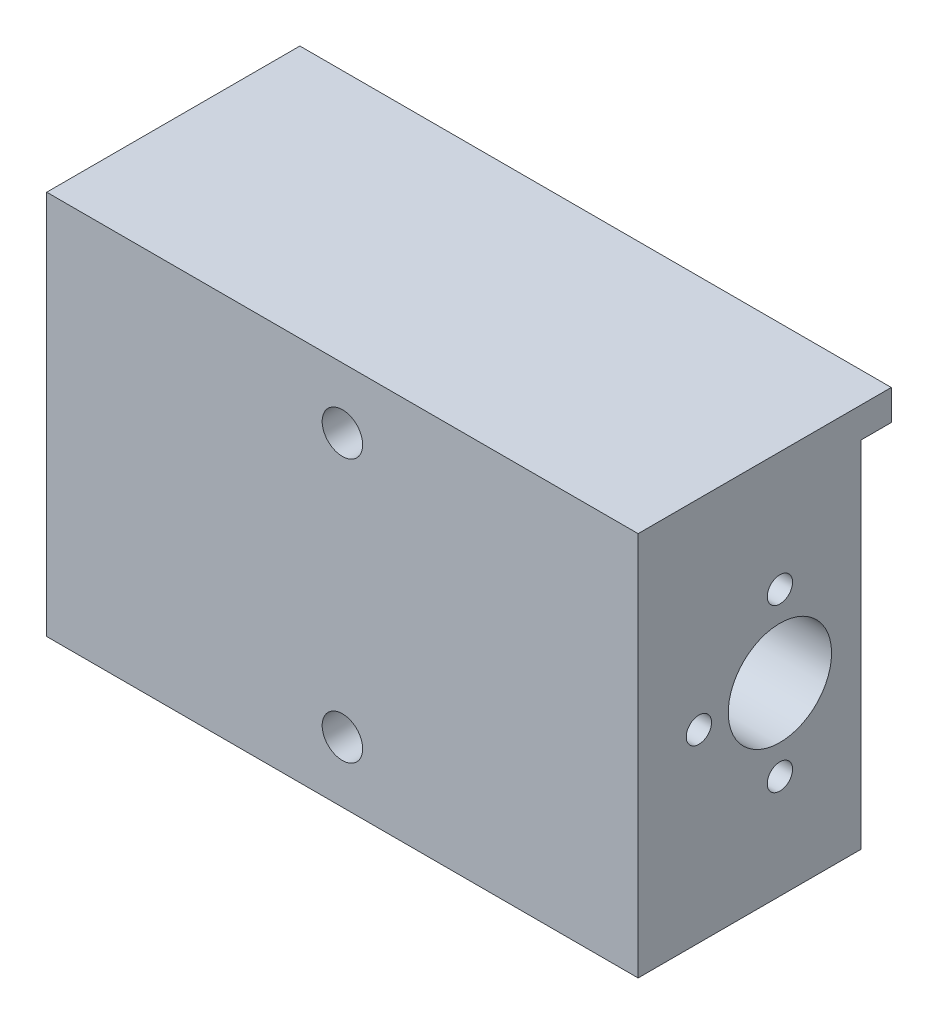
SolidWorks part; units mm, degrees
ref_plane "Alzado" through (0, 0, 0) normal (0, 0, 1) x (1, 0, 0)
ref_plane "Planta" through (0, 0, 0) normal (0, 1, 0) x (1, 0, 0)
ref_plane "Vista lateral" through (0, 0, 0) normal (1, 0, 0) x (0, 0, -1)
sketch "Croquis1" plane through (0, 0, 0) normal (0, 0, 1) x (1, 0, 0)
  line L1 (0, 0) -> (58.4, 0)
  line L2 (0, 0) -> (0, 38)
  line L3 (0, 38) -> (58.4, 38)
  line L4 (58.4, 0) -> (58.4, 38)
  dimension "D1" = 38
  dimension "D2" = 58.4
extrude "Saliente-Extruir1" add sketch "Croquis1" along normal blind 22
sketch "Croquis2" plane through (58.4, 0, 0) normal (1, 0, 0) x (0, 0, -1)
  circle A0 centre (-8, 18.2363) radius 5.1
  dimension "D1" = 10.2
  dimension "D2" = 8
extrude "Cortar-Extruir1" cut sketch "Croquis2" against normal through all
hole_wizard "Taladros de espiga de Ø4.0mm2" positions "Croquis4" profile "Croquis5" hole size "Ø4.0" standard "DIN"
sketch "Croquis4" plane through (0, 0, 22) normal (0, 0, 1) x (1, 0, 0)
  line L0 (0, 32) -> (58.4, 32) construction
  line L1 (0, 38) -> (0, 0) construction
  line L2 (58.4, 0) -> (58.4, 38) construction
  line L5 (58.4, 6) -> (0, 6) construction
  line L7 (58.4, 38) -> (0, 38) construction
  line L8 (29.2, 38) -> (29.2, 0) construction
  line L9 (0, 0) -> (58.4, 0) construction
  point P24 (29.2, 32)
  point P26 (29.2, 6)
  dimension "D1" = 6
  dimension "D2" = 6
sketch "Croquis5" plane through (29.2, 6, 22) normal (1, 0, 0) x (0, -1, 0)
  line L0 (0, 0) -> (0, 15.2017)
  line L1 (0, 15.2017) -> (2, 14)
  line L2 (2, 14) -> (2, 0)
  line L5 (2, 0) -> (0, 0)
  line L10 (0, 15.2017) -> (-2, 14) construction
  line L11 (0, -6.35) -> (0, 107.95) construction
  dimension "Diámetro de taladro" = 4
  dimension "Profundidad de taladro" = 14
  dimension "Ángulo de perforador" = 118
sketch "Croquis6" plane through (0, 0, 0) normal (0, 0, -1) x (-1, 0, 0)
  line L1 (-58.4, 35) -> (0, 35)
  line L2 (-58.4, 35) -> (-58.4, 38)
  line L3 (-58.4, 38) -> (0, 38)
  line L4 (0, 35) -> (0, 38)
  dimension "D1" = 3
extrude "Saliente-Extruir2" add sketch "Croquis6" along normal blind 3
hole_wizard "Perforador para roscar para macho de roscar para M32" positions "Croquis10" profile "Croquis11" hole size "M3" standard "DIN"
sketch "Croquis10" plane through (58.4, 0, 0) normal (1, 0, 0) x (0, 0, -1)
  line L0 (-8, 10.2363) -> (-8, 26.2363) construction
  line L2 (-16, 18.2363) -> (-8, 18.2363) construction
  circle A0 centre (-8, 18.2363) radius 8 construction
  point P5 (-8, 10.2363)
  point P6 (-8, 26.2363)
  point P8 (-16, 18.2363)
  dimension "D1" = 16
sketch "Croquis11" plane through (58.4, 18.2363, 16) normal (0, 1, 0) x (0, 0, -1)
  line L0 (0, 0) -> (0, 14.7511)
  line L1 (0, 14.7511) -> (1.25, 14)
  line L2 (1.25, 14) -> (1.25, 0)
  line L5 (1.25, 0) -> (0, 0)
  line L10 (0, 14.7511) -> (-1.25, 14) construction
  line L11 (0, -6.35) -> (0, 107.95) construction
  dimension "Diámetro de taladro" = 2.5
  dimension "Profundidad de taladro" = 14
  dimension "Ángulo de perforador" = 118
